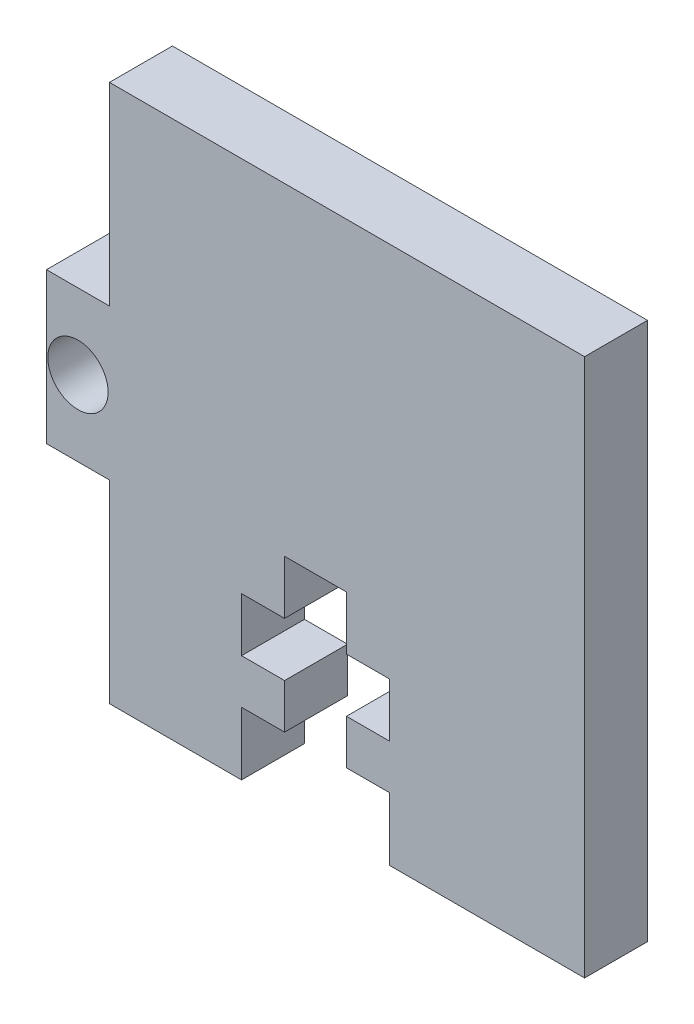
SolidWorks part; units mm, degrees
ref_plane "Front Plane" through (0, 0, 0) normal (0, 0, 1) x (1, 0, 0)
ref_plane "Top Plane" through (0, 0, 0) normal (0, 1, 0) x (1, 0, 0)
ref_plane "Right Plane" through (0, 0, 0) normal (1, 0, 0) x (0, 0, -1)
sketch "Sketch1" plane through (0, 0, 0) normal (0, 0, 1) x (1, 0, 0)
  line L0 (2.9718, 25.4) -> (2.9718, 16.256)
  line L1 (0, 0) -> (25.4, 0)
  line L2 (0, 0) -> (0, 25.4)
  line L3 (0, 25.4) -> (25.4, 25.4)
  line L4 (25.4, 0) -> (25.4, 25.4)
  line L5 (2.9718, 16.256) -> (0, 16.256)
  line L6 (0, 16.256) -> (0, 9.144)
  line L7 (0, 9.144) -> (2.9718, 9.144)
  line L8 (2.9718, 9.144) -> (2.9718, 0)
  line L9 (25.4, 0) -> (0, 0)
  line L11 (12.7, 25.4) -> (12.7, 0) construction
  line L12 (9.2075, 0) -> (9.2075, 2.9718)
  line L13 (9.2075, 2.9718) -> (11.2395, 2.9718)
  line L14 (11.2395, 2.9718) -> (11.2395, 5.08)
  line L15 (11.2395, 5.08) -> (9.2075, 5.08)
  line L16 (9.2075, 5.08) -> (9.2075, 7.62)
  line L17 (9.2075, 7.62) -> (11.2395, 7.62)
  line L18 (11.2395, 7.62) -> (11.2395, 10.16)
  line L19 (11.2395, 10.16) -> (14.1605, 10.16)
  line L20 (16.1925, 0) -> (16.1925, 2.9718)
  line L21 (16.1925, 2.9718) -> (14.1605, 2.9718)
  line L22 (14.1605, 2.9718) -> (14.1605, 5.08)
  line L23 (14.1605, 5.08) -> (16.1925, 5.08)
  line L24 (16.1925, 5.08) -> (16.1925, 7.62)
  line L25 (16.1925, 7.62) -> (14.1605, 7.62)
  line L26 (14.1605, 7.62) -> (14.1605, 10.16)
  circle A0 centre (1.4859, 12.7) radius 1.4224
  point P13 (0, 0)
  point P14 (0, 12.7)
  point P17 (0, 0)
  point P18 (12.7, 0)
  point P37 (12.7, 10.16)
  point P38 (36.005, 0)
  point P39 (25.6432, 0)
  dimension "D6" = 2.8448
  dimension "D8" = 1.4605
  dimension "D1" = 25.4
  dimension "D2" = 25.4
  dimension "D3" = 7.112
  dimension "D4" = 2.9718
  dimension "D5" = 9.144
  dimension "D7" = 1.4859
  dimension "D9" = 10.16
  dimension "D10" = 2.9718
  dimension "D11" = 3.4925
  dimension "D12" = 2.54
  dimension "D13" = 5.08
extrude "Boss-Extrude1" add sketch "Sketch1" along normal blind 2.9718 contours L11 L3 L0 L5 L2 L7 L8 L1 L12 L13 L14 L15 L16 L17 L18 L19 A0 | L3 L11 L19 L26 L25 L24 L23 L22 L21 L20 L1 L4 region at (7.0645, 13.6056, 0) region at (19.4775, 13.4202, 0)
